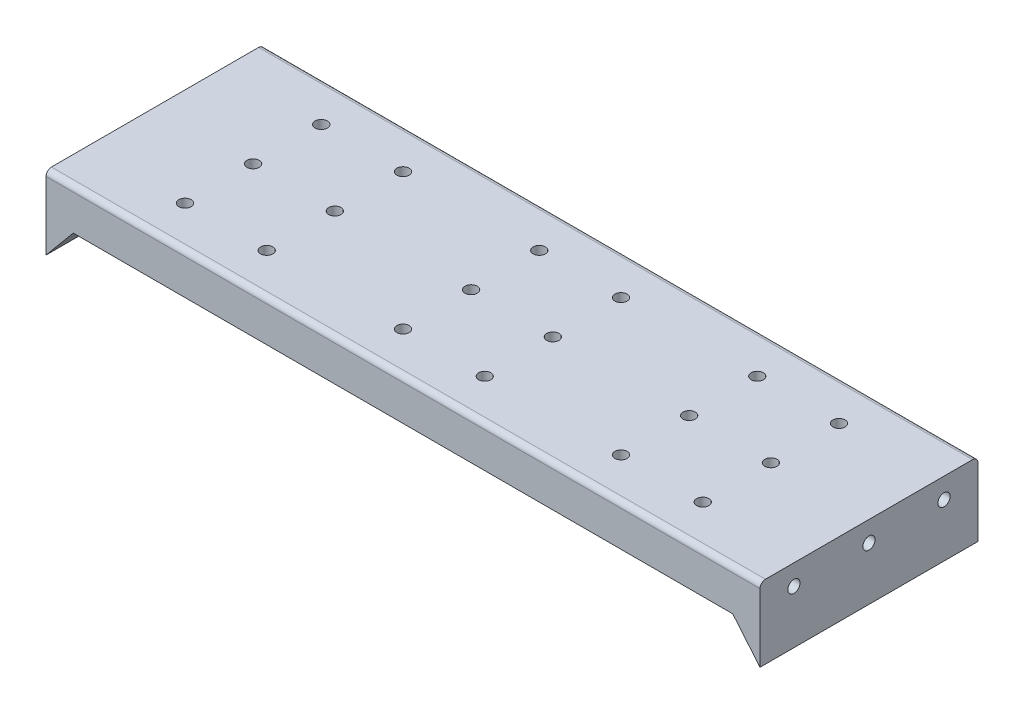
SolidWorks part; units mm, degrees
ref_plane "Front Plane" through (0, 0, 0) normal (0, 0, 1) x (1, 0, 0)
ref_plane "Top Plane" through (0, 0, 0) normal (0, 1, 0) x (1, 0, 0)
ref_plane "Right Plane" through (0, 0, 0) normal (1, 0, 0) x (0, 0, -1)
sketch "Sketch1" plane through (0, 0, 0) normal (0, 1, 0) x (1, 0, 0)
  line L1 (-131, 40) -> (131, 40)
  line L2 (-131, 40) -> (-131, -40)
  line L3 (-131, -40) -> (131, -40)
  line L4 (131, 40) -> (131, -40)
  line L5 (-131, 40) -> (131, -40) construction
  line L6 (-131, -40) -> (131, 40) construction
  point P0 (0, 0)
  dimension "D1" = 80
  dimension "D2" = 262
extrude "Boss-Extrude1" add sketch "Sketch1" along normal blind 15
sketch "Sketch2" plane through (-131, 0, 0) normal (-1, 0, 0) x (0, 0, 1)
  line L0 (-40, 7.5) -> (40, 7.5) construction
  line L1 (-40, 15) -> (-40, 0) construction
  line L2 (40, 15) -> (40, 0) construction
  line L3 (0, 0) -> (0, 15) construction
  line L4 (-40, 15) -> (40, 15) construction
  circle A0 centre (0, 7.5) radius 2.25
  circle A1 centre (-27.5436, 7.5) radius 2.25
  circle A2 centre (27.5436, 7.5) radius 2.25
  dimension "D1" = 4.5
  dimension "D2" = 4.5
extrude "Cut-Extrude1" cut sketch "Sketch2" against normal blind 40
ref_plane "Plane1" through (-121, 0, 0) normal (-1, 0, 0) x (0, 0, 1)
sketch "Sketch3" plane through (-121, 0, 0) normal (-1, 0, 0) x (0, 0, 1)
  line L0 (-31.2936, 5.3349) -> (-31.2936, 0)
  line L1 (0, 11.8301) -> (-3.75, 9.6651)
  line L2 (-3.75, 9.6651) -> (-3.75, 5.3349)
  line L5 (3.75, 5.3349) -> (3.75, 9.6651)
  line L6 (3.75, 9.6651) -> (0, 11.8301)
  line L7 (-27.5436, 11.8301) -> (-31.2936, 9.6651)
  line L8 (-31.2936, 9.6651) -> (-31.2936, 5.3349)
  line L11 (-23.7936, 5.3349) -> (-23.7936, 9.6651)
  line L12 (-23.7936, 9.6651) -> (-27.5436, 11.8301)
  line L13 (-40, 0) -> (40, 0) construction
  line L15 (-3.75, 5.3349) -> (-3.75, 0)
  line L16 (3.75, 5.3349) -> (3.75, 0)
  line L17 (-31.2936, 0) -> (-23.7936, 0)
  line L18 (-25.6686, 4.2524) -> (-23.7936, 5.3349) [skipped]
  line L19 (-31.2936, 5.3349) -> (-29.4186, 4.2524) [skipped]
  line L20 (-1.875, 4.2524) -> (0, 3.1699) [skipped]
  line L21 (1.875, 4.2524) -> (3.75, 5.3349) [skipped]
  line L22 (-3.75, 0) -> (3.75, 0)
  line L23 (0, 0) -> (0, 15) construction
  line L24 (-40, 15) -> (40, 15) construction
  line L25 (31.2936, 5.3349) -> (31.2936, 0)
  line L26 (31.2936, 9.6651) -> (31.2936, 5.3349)
  line L27 (27.5436, 11.8301) -> (31.2936, 9.6651)
  line L28 (23.7936, 9.6651) -> (27.5436, 11.8301)
  line L29 (23.7936, 5.3349) -> (23.7936, 9.6651)
  line L30 (23.7936, 5.3349) -> (23.7936, 0)
  line L31 (31.2936, 0) -> (23.7936, 0)
  line L32 (-23.7936, 5.3349) -> (-23.7936, 0)
  circle A0 centre (0, 7.5) radius 3.75 construction
  circle A1 centre (-27.5436, 7.5) radius 3.75 construction
  point P44 (0, 0)
  dimension "D1" = 7.5
  dimension "D2" = 7.5
extrude "Cut-Extrude2" cut sketch "Sketch3" against normal blind 3.5
mirror "Mirror1" about plane through (0, 0, 0) normal (1, 0, 0) of "Cut-Extrude1", "Cut-Extrude2"
sketch "Sketch4" plane through (0, 15, 0) normal (0, 1, 0) x (1, 0, 0)
  line L0 (-131, 0) -> (131, 0) construction
  line L1 (-131, 40) -> (-131, -40) construction
  line L2 (131, -40) -> (131, 40) construction
  line L3 (0, 40) -> (0, -40) construction
  line L4 (131, 40) -> (-131, 40) construction
  line L5 (-131, -40) -> (131, -40) construction
  line L6 (-15, 40) -> (-15, -40) construction
  circle A0 centre (-15, 0) radius 2.25
  circle A1 centre (-15, 25) radius 2.25
  circle A2 centre (-15, -25) radius 2.25
  circle A3 centre (15, -25) radius 2.25
  circle A4 centre (15, 0) radius 2.25
  circle A5 centre (15, 25) radius 2.25
  dimension "D1" = 4.5
  dimension "D2" = 4.5
  dimension "D3" = 50
  dimension "D4" = 30
extrude "Cut-Extrude3" cut sketch "Sketch4" against normal through all
pattern_linear "LPattern1" count 2 spacing 80 along (1, 0, 0) count 2 spacing 80 along (-1, 0, 0) of "Cut-Extrude3" pattern seed only yes
fillet "Fillet1" radius 2 2 edges at (0, 15, -40) (0, 15, 40)
sketch "Sketch7" plane through (0, 0, 40) normal (0, 0, 1) x (1, 0, 0)
  line L0 (-131, 0) -> (-131, -12)
  line L1 (-131, -12) -> (-121, 0)
  line L2 (-121, 0) -> (-131, 0)
  line L3 (-131, 0) -> (131, 0) construction
  point P5 (-115.1424, 0)
  dimension "D1" = 12
  dimension "D2" = 10
extrude "Boss-Extrude2" add sketch "Sketch7" against normal through all
mirror "Mirror2" about plane through (0, 0, 0) normal (1, 0, 0) of "Boss-Extrude2"
